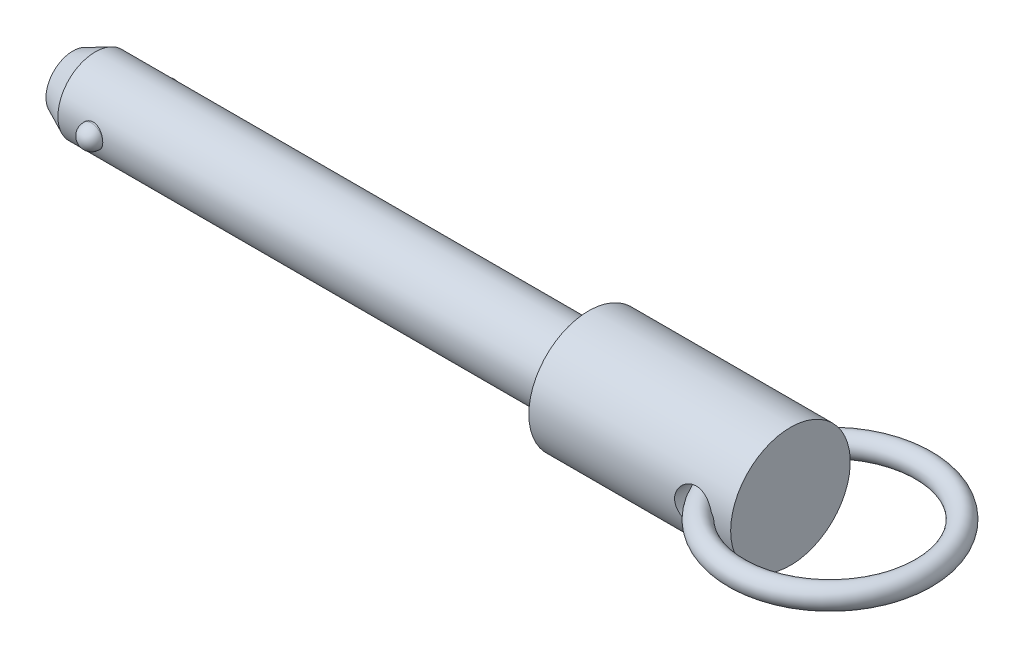
SolidWorks part; units mm, degrees
ref_plane "Front Plane" through (0, 0, 0) normal (0, 0, 1) x (1, 0, 0)
ref_plane "Top Plane" through (0, 0, 0) normal (0, 1, 0) x (1, 0, 0)
ref_plane "Right Plane" through (0, 0, 0) normal (1, 0, 0) x (0, 0, -1)
sketch "Sketch1" plane through (0, 0, 0) normal (0, 1, 0) x (1, 0, 0)
  line L0 (0, 0) -> (0, 5) construction
  line L1 (0, 5) -> (-9, 5)
  line L2 (-9, 5) -> (-9, 0)
  line L3 (0, 0) -> (8679.5741, 0) construction
  line L4 (0, 5) -> (60, 5)
  line L5 (60, 5) -> (60, 8)
  line L6 (60, 8) -> (87, 8)
  line L7 (87, 8) -> (87, 0)
  line L8 (-9, 0) -> (87, 0)
  dimension "D1" = 10
  dimension "D2" = 60
  dimension "D3" = 27
  dimension "D4" = 16
  dimension "D5" = 9
revolve "Revolve1" add sketch "Sketch1" angle 360 about L3
chamfer "Chamfer1" distance 3 angle 25 1 edges at (-9, 0, 5) first distance on face at (-9, 0, 5)
sketch "Sketch2" plane through (0, 0, 0) normal (0, 1, 0) x (1, 0, 0)
  line L0 (0, -6.5) -> (0, 6.5)
  line L1 (0, 6.5) -> (-1.5, 6.5)
  line L2 (-1.5, 6.5) -> (-1.5, -6.5)
  line L3 (-1.5, -6.5) -> (0, -6.5)
  line L4 (-1.5, 7.7558) -> (-1.5, 50007.7558) construction
  line L5 (-6, -5) -> (60, -5) construction
  line L6 (-6, -5) -> (60, -5) construction
  point P4 (0, 0)
  dimension "D1" = 3
  dimension "D2" = 1.5
revolve "Revolve2" add sketch "Sketch2" angle 360 about L4
fillet "Fillet1" radius 1.5 2 edges at (0, 0, -6.5) (0, 0, 6.5)
sketch "Sketch3" plane through (0, 0, 0) normal (0, 0, 1) x (1, 0, 0)
  line L0 (87, -8) -> (87, 8) construction
  line L1 (87, -8) -> (87, 8) construction
  line L2 (87, 0) -> (82, 0) construction
  circle A0 centre (82, 0) radius 2.5
  dimension "D1" = 5
  dimension "D2" = 5
extrude "Cut-Extrude1" cut sketch "Sketch3" against normal through all both and the other way through all
sketch "Sketch5" plane through (0, 0, 0) normal (0, 0, 1) x (1, 0, 0)
  line L0 (0, 0) -> (92.2938, 0) construction
  circle A0 centre (79.7938, 0) radius 1.5
  dimension "D2" = 3
  dimension "D1" = 12.5
ref_axis "Axis1" through (92.2938, 0, 0) along (0, 1, 0)
revolve "Revolve3" add sketch "Sketch5" angle 360 about axis through (92.2938, 0, 0) along (0, 1, 0)
